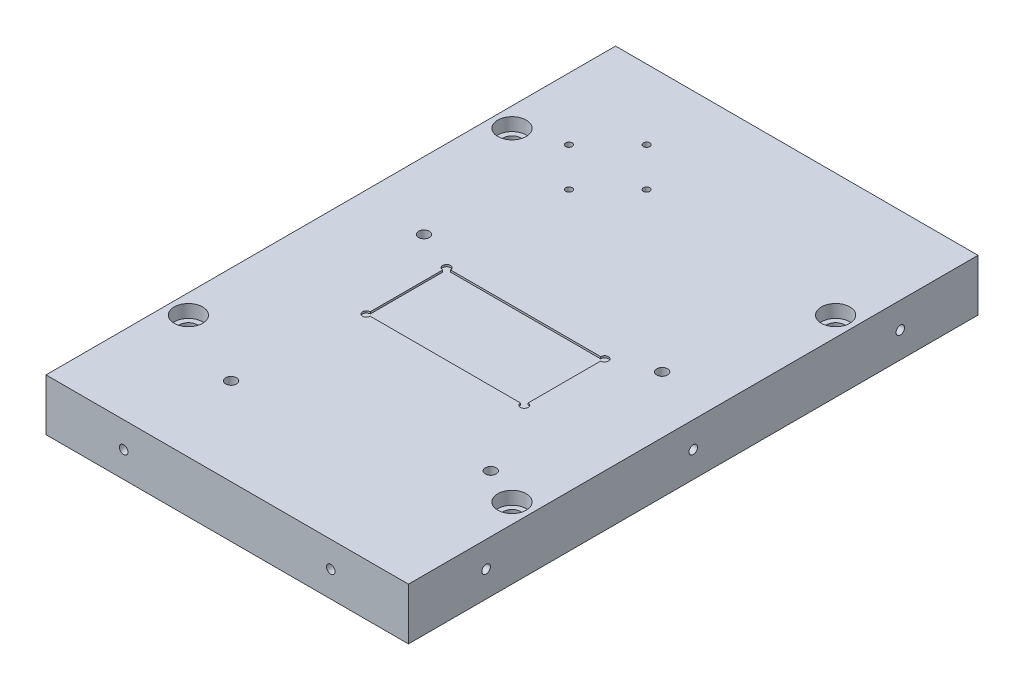
SolidWorks part; units mm, degrees
ref_plane "Front Plane" through (0, 0, 0) normal (0, 0, 1) x (1, 0, 0)
ref_plane "Top Plane" through (0, 0, 0) normal (0, 1, 0) x (1, 0, 0)
ref_plane "Right Plane" through (0, 0, 0) normal (1, 0, 0) x (0, 0, -1)
sketch "Sketch1" plane through (0, 0, 0) normal (0, 1, 0) x (1, 0, 0)
  line L1 (-70, -110) -> (70, -110)
  line L2 (-70, -110) -> (-70, 110)
  line L3 (-70, 110) -> (70, 110)
  line L4 (70, -110) -> (70, 110)
  line L5 (-70, -110) -> (70, 110) construction
  line L6 (-70, 110) -> (70, -110) construction
  point P0 (0, 0)
  dimension "D1" = 220
  dimension "D2" = 140
extrude "Boss-Extrude1" add sketch "Sketch1" along normal blind 20
hole_wizard "M4 Tapped Hole1" positions "Sketch3" profile "Sketch2" tap size "M4" standard "ISO"
sketch "Sketch3" plane through (0, 0, -110) normal (0, 0, -1) x (-1, 0, 0)
  circle A0 centre (-40, 10) radius 2.25 construction
  circle A1 centre (40, 10) radius 2.25 construction
  point P0 (-40, 10)
  point P3 (40, 10)
sketch "Sketch2" plane through (40, 10, -110) normal (1, 0, 0) x (0, 1, 0)
  line L0 (0, 0) -> (0, 12.4914)
  line L1 (0, 12.4914) -> (1.65, 11.5)
  line L2 (1.65, 11.5) -> (1.65, 0)
  line L5 (1.65, 0) -> (0, 0)
  line L10 (0, 12.4914) -> (-1.65, 11.5) construction
  line L11 (0, -6.35) -> (0, 107.95) construction
  dimension "Tap Drill Dia." = 3.3
  dimension "Tap Drill Depth" = 11.5
  dimension "Drill Angle" = 118
sketch "Sketch4" plane through (70, 0, 0) normal (1, 0, 0) x (0, 0, -1)
  line L0 (-110, 0) -> (110, 0) construction
  point P0 (-60, 10)
  dimension "D1" = 60
  dimension "D2" = 10
hole_wizard "M5 Tapped Hole1" positions "Sketch8" profile "Sketch7" tap size "M5" standard "ISO"
sketch "Sketch8" plane through (0, 20, 0) normal (0, 1, 0) x (1, 0, 0)
  circle A0 centre (-44, 10) radius 3.65 construction
  circle A1 centre (48, 10) radius 3.65 construction
  circle A4 centre (-32.253, -76.253) radius 3.65 construction
  circle A5 centre (48, -56.2044) radius 3.65 construction
  point P0 (-44, 10)
  point P3 (48, 10)
  point P6 (48, -56.2044)
  point P14 (-32.253, -76.253)
sketch "Sketch7" plane through (-44, 20, -10) normal (1, 0, 0) x (0, 0, 1)
  line L0 (0, 0) -> (0, 15.2618)
  line L1 (0, 15.2618) -> (2.1, 14)
  line L2 (2.1, 14) -> (2.1, 0)
  line L5 (2.1, 0) -> (0, 0)
  line L10 (0, 15.2618) -> (-2.1, 14) construction
  line L11 (0, -6.35) -> (0, 107.95) construction
  dimension "Tap Drill Dia." = 4.2
  dimension "Tap Drill Depth" = 14
  dimension "Drill Angle" = 118
cosmetic thread "Hole Thread1" parameters "D1"=10, "D2"=5
cosmetic thread "Hole Thread2" parameters "D1"=10, "D2"=5
cosmetic thread "Hole Thread3" parameters "D1"=10, "D2"=5
cosmetic thread "Hole Thread4" parameters "D1"=10, "D2"=5
sketch "Sketch9" plane through (0, 20, 0) normal (0, 1, 0) x (1, 0, 0)
  line L1 (-28.5, 3.25) -> (32.5, 3.25)
  line L2 (-28.5, 3.25) -> (-28.5, -27.75)
  line L3 (-28.5, -27.75) -> (32.5, -27.75)
  line L4 (32.5, 3.25) -> (32.5, -27.75)
  line L5 (32.25, 2.75) -> (2.25, 2.75) construction
  line L6 (-28.25, 2.75) -> (-28.25, -27.25) construction
  dimension "D1" = 61
  dimension "D2" = 31
  dimension "D3" = 0.5
  dimension "D4" = 0.25
extrude "Cut-Extrude1" cut sketch "Sketch9" against normal blind 0.75
hole_wizard "Ø3.0 (3) Diameter Hole1" positions "Sketch11" profile "Sketch10" hole size "Ø3.0" standard "ISO"
sketch "Sketch11" plane through (0, 20, 0) normal (0, 1, 0) x (1, 0, 0)
  point P22 (-28.5, 3.25)
  point P25 (-28.5, -27.75)
  point P28 (32.5, -27.75)
  point P31 (32.5, 3.25)
sketch "Sketch10" plane through (-28.5, 20, -3.25) normal (1, 0, 0) x (0, 0, 1)
  line L0 (0, 0) -> (0, 1.6503)
  line L1 (0, 1.6503) -> (1.5, 0.749)
  line L2 (1.5, 0.749) -> (1.5, 0)
  line L5 (1.5, 0) -> (0, 0)
  line L10 (0, 1.6503) -> (-1.5, 0.749) construction
  line L11 (0, -6.35) -> (0, 107.95) construction
  dimension "Hole Dia." = 3
  dimension "Hole Depth" = 0.749
  dimension "Drill Angle" = 118
sketch "casing lid fixture holes" plane through (70, 0, 0) normal (1, 0, 0) x (0, 0, -1)
  line L1 (0, 0) -> (0, 20) construction
  line L2 (-110, 20) -> (110, 20) construction
  point P0 (-80, 10)
  point P4 (80, 10)
  point P8 (0, 10)
  dimension "D1" = 80
hole_wizard "M4 Tapped Hole5" positions "Sketch31" profile "Sketch30" tap size "M4" standard "ISO"
sketch "Sketch31" plane through (70, 0, 0) normal (1, 0, 0) x (0, 0, -1)
  point P0 (0, 10)
  point P3 (80, 10)
  point P6 (-80, 10)
sketch "Sketch30" plane through (70, 10, 0) normal (0, 1, 0) x (0, 0, -1)
  line L0 (0, 0) -> (0, 12.4914)
  line L1 (0, 12.4914) -> (1.65, 11.5)
  line L2 (1.65, 11.5) -> (1.65, 0)
  line L5 (1.65, 0) -> (0, 0)
  line L10 (0, 12.4914) -> (-1.65, 11.5) construction
  line L11 (0, -6.35) -> (0, 107.95) construction
  dimension "Tap Drill Dia." = 3.3
  dimension "Tap Drill Depth" = 11.5
  dimension "Drill Angle" = 118
sketch "optical breadboard holes" plane through (0, 20, 0) normal (0, 1, 0) x (1, 0, 0)
  line L1 (-62.5, -62.5) -> (62.5, -62.5) construction
  line L2 (-62.5, -62.5) -> (-62.5, 62.5) construction
  line L3 (-62.5, 62.5) -> (62.5, 62.5) construction
  line L4 (62.5, -62.5) -> (62.5, 62.5) construction
  line L5 (-62.5, -62.5) -> (62.5, 62.5) construction
  line L6 (-62.5, 62.5) -> (62.5, -62.5) construction
  point P0 (0, 0)
  dimension "D1" = 125
  dimension "D2" = 125
hole_wizard "CBORE for M6 Hex Socket Head Cap Screw2" positions "Sketch24" profile "Sketch23" counterbore size "M6" standard "ISO" end condition through all
sketch "Sketch24" plane through (0, 20, 0) normal (0, 1, 0) x (1, 0, 0)
  point P0 (-62.5, 62.5)
  point P3 (62.5, 62.5)
  point P6 (62.5, -62.5)
  point P9 (-62.5, -62.5)
sketch "Sketch23" plane through (-62.5, 20, -62.5) normal (1, 0, 0) x (0, 0, 1)
  line L0 (0, 0) -> (0, 20)
  line L1 (0, 20) -> (3.5, 20)
  line L3 (3.5, 20) -> (3.5, 5)
  line L4 (3.5, 5) -> (5.5, 5)
  line L5 (5.5, 5) -> (5.5, 0)
  line L7 (5.5, 0) -> (0, 0)
  line L11 (0, -6.35) -> (0, 107.95) construction
  dimension "Thru Hole Dia." = 7
  dimension "Thru Hole Depth" = 20
  dimension "C'Bore Dia." = 11
  dimension "C'Bore Depth" = 5
hole_wizard "M3 Tapped Hole1" positions "Sketch28" profile "Sketch27" tap size "M3" standard "ISO"
sketch "Sketch28" plane through (0, 20, 0) normal (0, 1, 0) x (1, 0, 0)
  point P0 (-31, 83)
  point P3 (-16, 68)
  point P6 (-31, 53)
  point P9 (-46, 68)
sketch "Sketch27" plane through (-31, 20, -83) normal (1, 0, 0) x (0, 0, 1)
  line L0 (0, 0) -> (0, 9.2511)
  line L1 (0, 9.2511) -> (1.25, 8.5)
  line L2 (1.25, 8.5) -> (1.25, 0)
  line L5 (1.25, 0) -> (0, 0)
  line L10 (0, 9.2511) -> (-1.25, 8.5) construction
  line L11 (0, -6.35) -> (0, 107.95) construction
  dimension "Tap Drill Dia." = 2.5
  dimension "Tap Drill Depth" = 8.5
  dimension "Drill Angle" = 118
mirror "Mirror8" about plane through (0, 0, 0) normal (1, 0, 0) of "M4 Tapped Hole5"
mirror "Mirror9" about plane through (0, 0, 0) normal (0, 0, 1) of "M4 Tapped Hole1"
